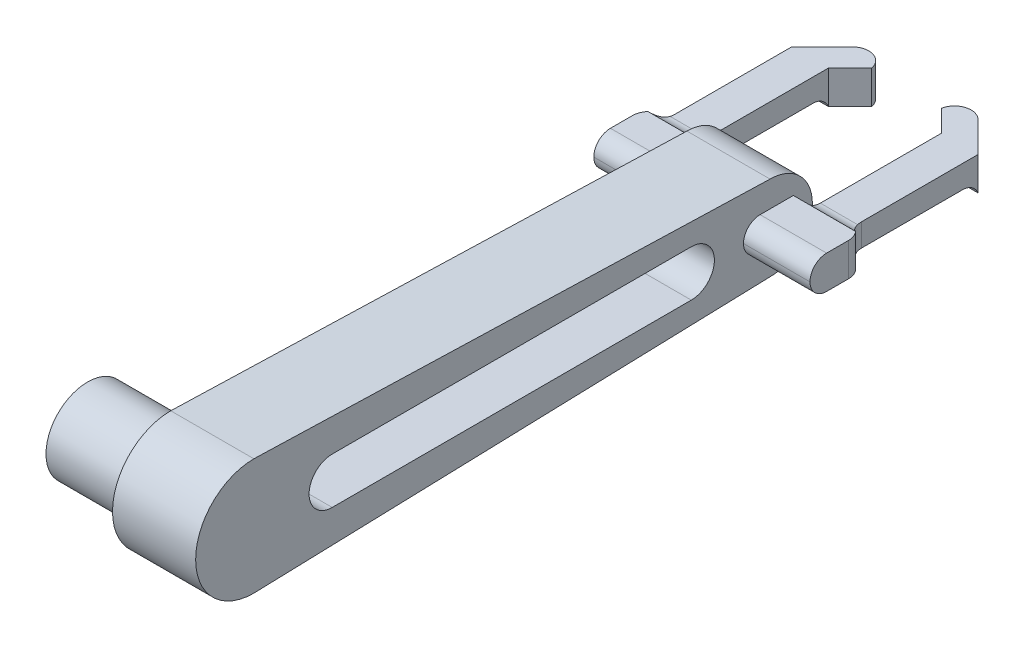
SolidWorks part; units mm, degrees
ref_plane "Ön Düzlem" through (0, 0, 0) normal (0, 0, 1) x (1, 0, 0)
ref_plane "Üst Düzlem" through (0, 0, 0) normal (0, 1, 0) x (1, 0, 0)
ref_plane "Sağ Düzlem" through (0, 0, 0) normal (1, 0, 0) x (0, 0, -1)
sketch "Çizim1" plane through (0, 0, 0) normal (1, 0, 0) x (0, 0, -1)
  line L0 (0, 35) -> (310.4288, 25.4559)
  line L1 (0, -35) -> (310.4288, -25.4559)
  arc A0 (0, 35) -> (0, -35) centre (0, 0) ccw
  arc A1 (310.4288, -25.4559) -> (310.4288, 25.4559) centre (310.4288, 0) ccw
  point P1 (0, 0)
  point P4 (0, 0)
  point P9 (0, 0)
  point P11 (0, 0)
  point P12 (0, 0)
  point P13 (0, 0)
  point P14 (0, 34.9339)
  point P15 (0, 0)
  point P16 (0, 0)
  dimension "D1" = 70
  dimension "D2" = 310.4288
extrude "Yükseklik-Ekstrüzyon1" add sketch "Çizim1" along normal blind 50
sketch "Çizim2" plane through (0, 0, 0) normal (-1, 0, 0) x (0, 0, 1)
  circle A0 centre (0, 0) radius 25
  dimension "D1" = 50
extrude "Yükseklik-Ekstrüzyon2" add sketch "Çizim2" along normal blind 50
sketch "Çizim3" plane through (50, 0, 0) normal (1, 0, 0) x (0, 0, -1)
  line L1 (324.433, -10.0918) -> (294.433, -10.0918)
  line L2 (324.433, -10.0918) -> (324.433, 9.9082)
  line L3 (324.433, 9.9082) -> (294.433, 9.9082)
  line L4 (294.433, -10.0918) -> (294.433, 9.9082)
  line L5 (324.433, -10.0918) -> (294.433, 9.9082) construction
  line L6 (324.433, 9.9082) -> (294.433, -10.0918) construction
  point P0 (309.433, -0.0918)
  dimension "D1" = 20
  dimension "D2" = 30
extrude "Yükseklik-Ekstrüzyon3" add sketch "Çizim3" along normal blind 40
ref_plane "Düzlem1" through (25, 0, 0) normal (1, 0, 0) x (0, 0, -1)
sketch "Çizim4" plane through (0, 0, -324.433) normal (0, 0, -1) x (-1, 0, 0)
  line L1 (-81.0472, 6.7672) -> (-58.9528, 6.7672)
  line L2 (-81.0472, 6.7672) -> (-81.0472, -6.9507)
  line L3 (-81.0472, -6.9507) -> (-58.9528, -6.9507)
  line L4 (-58.9528, 6.7672) -> (-58.9528, -6.9507)
  line L5 (-81.0472, 6.7672) -> (-58.9528, -6.9507) construction
  line L6 (-81.0472, -6.9507) -> (-58.9528, 6.7672) construction
  point P0 (-70, -0.0918)
extrude "Yükseklik-Ekstrüzyon4" add sketch "Çizim4" along normal blind 80
sketch "Çizim5" plane through (0, 6.7672, 0) normal (0, 1, 0) x (1, 0, 0)
  line L0 (81.0472, 404.433) -> (45.9276, 439.5526)
  line L1 (45.9276, 439.5526) -> (45.9276, 417.4582)
  line L2 (45.9276, 417.4582) -> (58.9528, 404.433)
  line L7 (58.9528, 324.433) -> (81.0472, 324.433)
  line L8 (81.0472, 324.433) -> (81.0472, 404.433)
  line L9 (81.0472, 404.433) -> (58.9528, 404.433)
  line L10 (58.9528, 404.433) -> (58.9528, 324.433)
  line L13 (81.0472, 404.433) -> (58.9528, 404.433)
  dimension "D1" = 0
extrude "Yükseklik-Ekstrüzyon5" add sketch "Çizim5" against normal blind 20
fillet "Radyus1" radius 10 3 edges at (70, -6.9507, -324.433) (81.0472, -0.0918, -324.433) (70, 6.7672, -324.433)
fillet "Radyus3" radius 10 1 edges at (90, -0.0918, -324.433)
fillet "Radyus4" radius 10 2 edges at (70, -10.0918, -294.433) (70, 9.9082, -294.433)
fillet "Radyus8" radius 10 1 edges at (45.9276, -3.2328, -439.5526)
fillet "Radyus9" radius 10 1 edges at (70, -6.9507, -404.433)
mirror "Aynalama2" about plane through (25, 0, 0) normal (1, 0, 0) of "Radyus4", "Radyus1", "Yükseklik-Ekstrüzyon5", "Radyus8", "Radyus3", "Yükseklik-Ekstrüzyon3", "Yükseklik-Ekstrüzyon4"
fillet "Radyus10" radius 10 1 edges at (-20, -6.9507, -404.433)
sketch "Çizim6" plane through (50, 0, 0) normal (1, 0, 0) x (0, 0, -1)
  line L0 (47.1096, 0) -> (263.059, 0) construction
  line L1 (47.1096, 13.8948) -> (263.059, 13.8948)
  line L2 (47.1096, -13.8948) -> (263.059, -13.8948)
  arc A0 (47.1096, 13.8948) -> (47.1096, -13.8948) centre (47.1096, 0) ccw
  arc A1 (263.059, -13.8948) -> (263.059, 13.8948) centre (263.059, 0) ccw
  point P3 (155.0843, 0)
  dimension "D1" = 215.9494
extrude "Kes-Ekstrüzyon1" cut sketch "Çizim6" against normal blind 60
